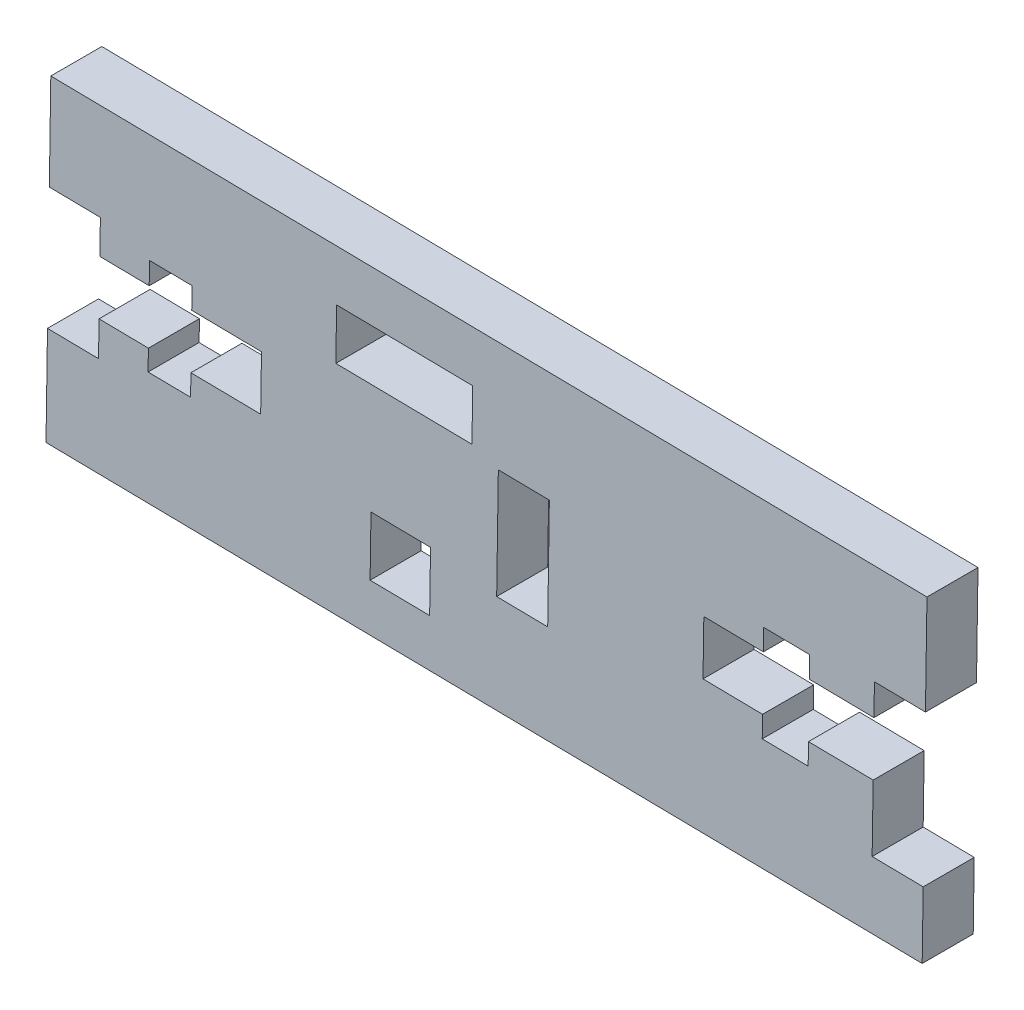
SolidWorks part; units mm, degrees
ref_plane "Plan de face" through (0, 0, 0) normal (0, 0, 1) x (1, 0, 0)
ref_plane "Plan de dessus" through (0, 0, 0) normal (0, 1, 0) x (1, 0, 0)
ref_plane "Plan de droite" through (0, 0, 0) normal (1, 0, 0) x (0, 0, -1)
sketch "Esquisse1" plane through (0, 0, 0) normal (0, 0, 1) x (1, 0, 0)
  line L0 (56.0026, 1451.9923) -> (107.4969, 1451.2258) construction
  line L1 (56.0115, 1451.9997) -> (107.5115, 1451.2284)
  line L2 (55.7296, 1433.2018) -> (107.2303, 1432.4305)
  line L3 (56.0115, 1451.9997) -> (55.9261, 1446.3003)
  line L4 (55.9261, 1446.3003) -> (58.9258, 1446.2554)
  line L5 (58.9258, 1446.2554) -> (58.8958, 1444.2556)
  line L7 (61.7955, 1444.2122) -> (61.815, 1445.5121)
  line L8 (61.815, 1445.5121) -> (64.3144, 1445.4746)
  line L9 (64.3144, 1445.4746) -> (64.2955, 1444.2122)
  line L10 (64.2955, 1444.2122) -> (68.3953, 1444.1508)
  line L11 (68.3953, 1444.1508) -> (68.3474, 1440.9508)
  line L12 (68.3474, 1440.9508) -> (64.2476, 1441.0122)
  line L13 (64.2476, 1441.0122) -> (64.2287, 1439.7523)
  line L14 (64.2287, 1439.7523) -> (61.7293, 1439.7898)
  line L15 (61.7293, 1439.7898) -> (61.7476, 1441.0126)
  line L16 (61.7476, 1441.0126) -> (58.8479, 1441.056)
  line L17 (58.8479, 1441.056) -> (58.8173, 1439.0111)
  line L18 (58.8173, 1439.0111) -> (55.8173, 1439.056)
  line L19 (55.8173, 1439.056) -> (55.7296, 1433.2018)
  line L20 (107.5115, 1451.2284) -> (107.4231, 1445.3251)
  line L21 (107.4231, 1445.3251) -> (104.4234, 1445.37)
  line L22 (104.4234, 1445.37) -> (104.3958, 1443.5269)
  line L23 (104.3958, 1443.5269) -> (100.5958, 1443.5838)
  line L24 (100.5958, 1443.5838) -> (100.6147, 1444.8436)
  line L25 (100.6147, 1444.8436) -> (97.9147, 1444.8841)
  line L26 (97.9147, 1444.8841) -> (97.8958, 1443.6242)
  line L27 (97.8958, 1443.6242) -> (94.3958, 1443.6766)
  line L28 (94.3958, 1443.6766) -> (94.3479, 1440.4766)
  line L29 (94.3479, 1440.4766) -> (97.8479, 1440.4242)
  line L30 (97.8479, 1440.4242) -> (97.829, 1439.1644)
  line L31 (97.829, 1439.1644) -> (100.529, 1439.1239)
  line L32 (100.529, 1439.1239) -> (100.5479, 1440.3838)
  line L33 (100.5479, 1440.3838) -> (104.3479, 1440.3269)
  line L34 (104.3479, 1440.3269) -> (104.2892, 1436.4069)
  line L35 (104.2892, 1436.4069) -> (107.2892, 1436.3619)
  line L36 (107.2892, 1436.3619) -> (107.2303, 1432.4305)
  line L37 (58.8958, 1444.2556) -> (61.7955, 1444.2122)
  line L38 (55.9374, 1444.2999) -> (62.5126, 1444.2015) construction
  line L46 (72.8115, 1448.7478) -> (80.8115, 1448.6279)
  line L47 (72.7666, 1445.7481) -> (80.7666, 1445.6283)
  line L48 (72.8115, 1448.7478) -> (72.7666, 1445.7481)
  line L49 (80.8115, 1448.6279) -> (80.7666, 1445.6283)
  line L50 (82.317, 1445.105) -> (82.2196, 1438.6057)
  line L51 (85.3166, 1445.0601) -> (85.2193, 1438.5608)
  line L52 (82.317, 1445.105) -> (85.3166, 1445.0601)
  line L53 (82.2196, 1438.6057) -> (85.2193, 1438.5608)
  line L54 (74.832, 1439.2164) -> (78.332, 1439.164)
  line L55 (78.332, 1439.164) -> (78.2796, 1435.6644)
  line L56 (78.2796, 1435.6644) -> (74.7796, 1435.7168)
  line L57 (74.7796, 1435.7168) -> (74.832, 1439.2164)
  dimension "D1" = 51.5
  dimension "D2" = 51.5
  dimension "D3" = 1451.9997
  dimension "D4" = 56.0115
  dimension "D5" = 18.8
  dimension "D6" = 5.7
  dimension "D7" = 3
  dimension "D8" = 90
  dimension "D9" = 6.4
  dimension "D10" = 90
  dimension "D11" = 90
  dimension "D12" = 3
  dimension "D13" = 90
  dimension "D14" = 90
  dimension "D15" = 90
  dimension "D16" = 90
  dimension "D17" = 90
  dimension "D18" = 2.9997
  dimension "D19" = 7.7
  dimension "D20" = 2.9
  dimension "D21" = 2.5
  dimension "D22" = 12.5
  dimension "D23" = 3.2
  dimension "D24" = 3.2
  dimension "D25" = 1.2626
  dimension "D26" = 1.26
  dimension "D27" = 2
  dimension "D28" = 3
  dimension "D29" = 3
  dimension "D30" = 1.8434
  dimension "D31" = 90
  dimension "D32" = 90
  dimension "D33" = 90
  dimension "D34" = 90
  dimension "D35" = 90
  dimension "D36" = 90
  dimension "D37" = 90
  dimension "D38" = 90
  dimension "D39" = 90
  dimension "D40" = 90
  dimension "D41" = 90
  dimension "D42" = 90
  dimension "D43" = 90
  dimension "D44" = 90
  dimension "D45" = 90
  dimension "D46" = 90
  dimension "D47" = 90
  dimension "D48" = 90
  dimension "D49" = 2.9997
  dimension "D50" = 5.904
  dimension "D51" = 3.8
  dimension "D52" = 1.26
  dimension "D53" = 2.7
  dimension "D54" = 1.26
  dimension "D55" = 3.5
  dimension "D56" = 3.2
  dimension "D57" = 1.26
  dimension "D58" = 1.26
  dimension "D59" = 3.5
  dimension "D60" = 2.7
  dimension "D61" = 3.8
  dimension "D62" = 3.92
  dimension "D63" = 3
  dimension "D64" = 3
  dimension "D65" = 8
  dimension "D66" = 8
  dimension "D67" = 90
  dimension "D68" = 90
  dimension "D69" = 3
  dimension "D70" = 16.8
  dimension "D71" = 90
  dimension "D72" = 3
  dimension "D73" = 6.5
  dimension "D74" = 90
  dimension "D75" = 90
  dimension "D76" = 6.5
  dimension "D77" = 22.1
  dimension "D78" = 90
  dimension "D79" = 90
  dimension "D80" = 3.5
  dimension "D81" = 3.5
  dimension "D82" = 3.5
  dimension "D83" = 3.4996
  dimension "D84" = 2.8
  dimension "D85" = 19.05
base flange "Tôle de base pliée1" sketch "Esquisse1" thickness 3 reverse thickness direction no parameters "D1"=1.5
sketch "Lignes de pliage1" [suppressed] plane through (0, 0, 0) normal (0, 1, 0) x (1, 0, 0)
sketch "Cube de visualisation1" [suppressed] plane through (0, 0, 0) normal (0, 1, 0) x (1, 0, 0)
sheet metal parameters "Tôlerie1" thickness 3 parameters "D1"=1.5
flat pattern "Etat déplié1" [suppressed]
sketch "Lignes de pliage2" plane through (0, 0, 0) normal (0, 1, 0) x (1, 0, 0)
sketch3d "Cube de visualisation2" [suppressed]
  line L0 (56.0117, 1452.001, 0) -> (107.5115, 1451.2284, 0) construction
  line L1 (55.7296, 1433.2031, 0) -> (107.2295, 1432.4305, 0) construction
  line L2 (56.0117, 1452.001, 0) -> (55.7296, 1433.2031, 0) construction
  line L3 (107.5115, 1451.2284, 0) -> (107.2295, 1432.4305, 0) construction
